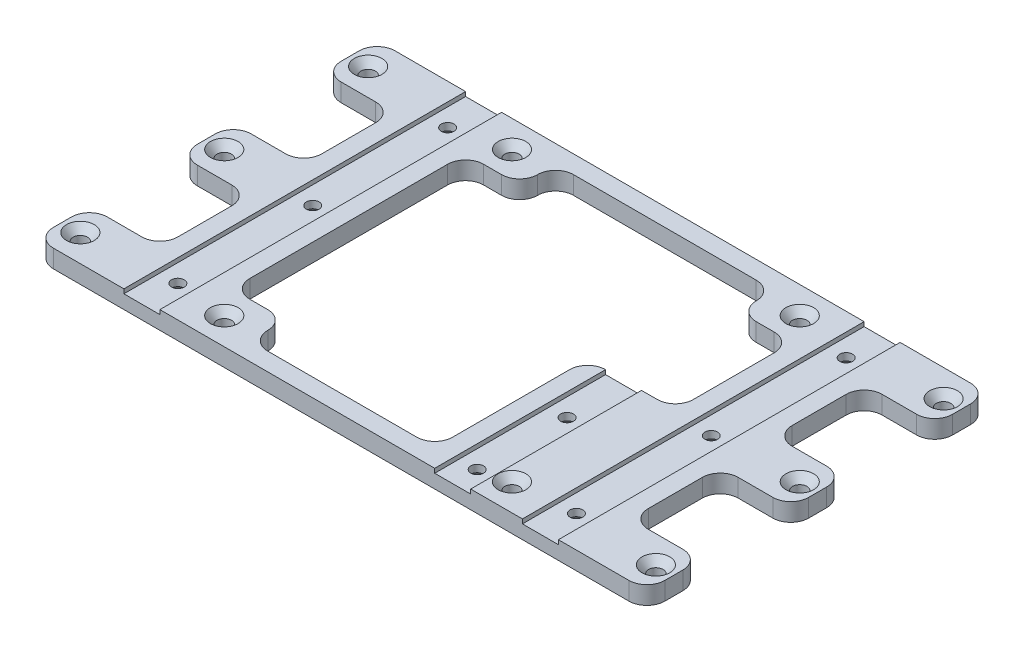
SolidWorks part; units mm, degrees
material "6061-T6 (SS)"
ref_plane "Front Plane" through (0, 0, 0) normal (0, 0, 1) x (1, 0, 0)
ref_plane "Top Plane" through (0, 0, 0) normal (0, 1, 0) x (1, 0, 0)
ref_plane "Right Plane" through (0, 0, 0) normal (1, 0, 0) x (0, 0, -1)
sketch "Sketch1" plane through (0, 0, 0) normal (0, 1, 0) x (1, 0, 0)
  line L1 (0, 0) -> (215.9, 0)
  line L2 (0, 0) -> (0, 120.65)
  line L3 (0, 120.65) -> (215.9, 120.65)
  line L4 (215.9, 0) -> (215.9, 120.65)
  dimension "D1" = 120.65
  dimension "D2" = 215.9
extrude "Boss-Extrude1" add sketch "Sketch1" along normal blind 6.35
hole_wizard "CSK for #10 Flat Head Machine Screw1" positions "Sketch3" profile "Sketch2" countersink size "#10" standard "Ansi Inch" end condition through all
sketch "Sketch3" plane through (0, 6.35, 0) normal (0, 1, 0) x (-1, 0, 0)
  line L0 (-107.95, 0) -> (-107.95, -120.65) construction
  line L1 (0, 0) -> (-215.9, 0) construction
  line L2 (-215.9, -120.65) -> (0, -120.65) construction
  line L4 (-215.9, -60.325) -> (0, -60.325) construction
  line L5 (-215.9, 0) -> (-215.9, -120.65) construction
  line L6 (0, -120.65) -> (0, 0) construction
  line L7 (-6.35, -111.125) -> (-209.55, -111.125) construction
  line L9 (-209.55, -111.125) -> (-209.55, -9.525) construction
  line L11 (-6.35, -111.125) -> (-6.35, -9.525) construction
  line L13 (-209.55, -9.525) -> (-6.35, -9.525) construction
  point P0 (-6.35, -111.125)
  point P1 (-209.55, -111.125)
  point P3 (-209.55, -9.525)
  point P5 (-6.35, -9.525)
  point P33 (-107.95, -111.125)
  point P41 (-6.35, -60.325)
  point P44 (-209.55, -60.325)
  point P54 (-158.75, -111.125)
  point P56 (-57.15, -111.125)
  point P58 (-57.15, -9.525)
  point P60 (-158.75, -9.525)
  dimension "D1" = 203.2
  dimension "D2" = 101.6
  dimension "D3" = 50.8
  dimension "D4" = 50.8
  dimension "D5" = 50.8
  dimension "D6" = 50.8
sketch "Sketch2" plane through (6.35, 6.35, -111.125) normal (1, 0, 0) x (0, 0, 1)
  line L0 (0, 0) -> (0, 6.35)
  line L1 (0, 6.35) -> (2.5527, 6.35)
  line L2 (2.5527, 6.35) -> (2.5527, 2.6882)
  line L3 (2.5527, 2.6882) -> (4.8895, 0)
  line L5 (4.8895, 0) -> (0, 0)
  line L6 (-2.5527, 2.6882) -> (-4.8895, 0) construction
  line L11 (0, -6.35) -> (0, 107.95) construction
  dimension "Thru Hole Dia." = 5.1054
  dimension "Thru Hole Depth" = 6.35
  dimension "Near C'Sink Dia." = 9.779
  dimension "Near C'Sink Angle" = 82
hole_wizard "CSK for #8 Flat Head Machine Screw1" positions "Sketch5" profile "Sketch6" countersink size "#8" standard "Ansi Inch" end condition through all
sketch "Sketch5" plane through (0, 0, 0) normal (0, -1, 0) x (1, 0, 0)
  line L0 (37.592, -12.7) -> (37.592, -107.95) construction
  line L3 (0, 0) -> (215.9, 0) construction
  line L5 (107.95, 0) -> (107.95, -120.65) construction
  line L6 (215.9, -120.65) -> (0, -120.65) construction
  point P0 (37.592, -12.7)
  point P8 (37.592, -60.325)
  point P10 (37.592, -107.95)
  point P27 (107.95, -60.325)
  dimension "D1" = 95.25
  dimension "D2" = 70.358
sketch "Sketch6" plane through (37.592, 0, -12.7) normal (1, 0, 0) x (0, 0, -1)
  line L0 (0, 0) -> (0, 6.35)
  line L1 (0, 6.35) -> (2.2479, 6.35)
  line L2 (2.2479, 6.35) -> (2.2479, 2.2645)
  line L3 (2.2479, 2.2645) -> (4.2164, 0)
  line L5 (4.2164, 0) -> (0, 0)
  line L6 (-2.2479, 2.2645) -> (-4.2164, 0) construction
  line L11 (0, -6.35) -> (0, 107.95) construction
  dimension "Thru Hole Dia." = 4.4958
  dimension "Thru Hole Depth" = 6.35
  dimension "Near C'Sink Dia." = 8.4328
  dimension "Near C'Sink Angle" = 82
ref_plane "Plane1" through (107.95, 0, 0) normal (-1, 0, 0) x (0, 0, 1)
mirror "Mirror1" about plane through (107.95, 0, 0) normal (-1, 0, 0) of "CSK for #8 Flat Head Machine Screw1"
hole_wizard "CSK for #8 Flat Head Machine Screw2" positions "Sketch8" profile "Sketch9" countersink size "#8" standard "Ansi Inch" end condition through all
sketch "Sketch8" plane through (0, 0, 0) normal (0, -1, 0) x (1, 0, 0)
  line L0 (147.3359, -8.636) -> (147.3359, -40.386) construction
  line L4 (0, 0) -> (215.9, 0) construction
  circle A2 centre (178.308, -12.7) radius 4.2164 construction
  point P0 (147.3359, -8.636)
  point P8 (147.3359, -40.386)
  dimension "D3" = 30.9721
  dimension "D1" = 31.75
  dimension "D2" = 8.636
sketch "Sketch9" plane through (147.3359, 0, -8.636) normal (1, 0, 0) x (0, 0, -1)
  line L0 (0, 0) -> (0, 6.35)
  line L1 (0, 6.35) -> (2.2479, 6.35)
  line L2 (2.2479, 6.35) -> (2.2479, 2.2645)
  line L3 (2.2479, 2.2645) -> (4.2164, 0)
  line L5 (4.2164, 0) -> (0, 0)
  line L6 (-2.2479, 2.2645) -> (-4.2164, 0) construction
  line L11 (0, -6.35) -> (0, 107.95) construction
  dimension "Thru Hole Dia." = 4.4958
  dimension "Thru Hole Depth" = 6.35
  dimension "Near C'Sink Dia." = 8.4328
  dimension "Near C'Sink Angle" = 82
sketch "Sketch10" plane through (0, 6.35, 0) normal (0, 1, 0) x (1, 0, 0)
  line L0 (37.592, 120.65) -> (37.592, 0) construction
  line L1 (215.9, 120.65) -> (0, 120.65) construction
  line L2 (0, 0) -> (215.9, 0) construction
  line L3 (178.308, 120.65) -> (178.308, 0) construction
  line L4 (147.3359, 120.65) -> (147.3359, 0) construction
  line L5 (37.592, 19.05) -> (37.592, 0) construction
  line L6 (178.308, 6.35) -> (178.308, 0) construction
  line L7 (147.3359, 8.636) -> (147.3359, 0) construction
  line L8 (31.242, 120.65) -> (31.242, 0)
  line L9 (171.958, 120.65) -> (171.958, 0)
  line L10 (140.9859, 63.5) -> (140.9859, 0)
  line L11 (43.942, 120.65) -> (43.942, 0)
  line L12 (184.658, 120.65) -> (184.658, 0)
  line L13 (153.6859, 63.5) -> (153.6859, 0)
  line L14 (31.242, 120.65) -> (43.942, 120.65)
  line L15 (43.942, 0) -> (31.242, 0)
  line L16 (171.958, 0) -> (184.658, 0)
  line L17 (140.9859, 0) -> (153.6859, 0)
  line L18 (171.958, 120.65) -> (184.658, 120.65)
  line L19 (140.9859, 120.65) -> (140.9859, 0) construction
  line L20 (37.592, 107.95) -> (37.592, 120.65) construction
  line L21 (215.9, 120.65) -> (0, 120.65) construction
  line L22 (178.308, 107.95) -> (178.308, 120.65) construction
  line L23 (147.3359, 107.95) -> (147.3359, 120.65) construction
  line L24 (153.6859, 120.65) -> (153.6859, 0) construction
  line L25 (140.9859, 63.5) -> (153.6859, 63.5)
  line L26 (215.9, 120.65) -> (0, 120.65) construction
  dimension "D3" = 57.15
  dimension "D1" = 6.35
  dimension "D2" = 6.35
extrude "Cut-Extrude1" cut sketch "Sketch10" against normal blind 1.524
sketch "Sketch13" plane through (0, 6.35, 0) normal (0, 1, 0) x (1, 0, 0)
  line L0 (0, 120.65) -> (0, 0) construction
  line L1 (0, 101.6) -> (24.892, 101.6)
  line L2 (0, 101.6) -> (0, 69.85)
  line L3 (0, 69.85) -> (24.892, 69.85)
  line L4 (24.892, 101.6) -> (24.892, 69.85)
  line L5 (24.892, 69.85) -> (24.892, 50.8) construction
  line L6 (0, 50.8) -> (24.892, 50.8)
  line L7 (0, 50.8) -> (0, 19.05)
  line L8 (0, 19.05) -> (24.892, 19.05)
  line L9 (24.892, 50.8) -> (24.892, 19.05)
  line L10 (0, 120.65) -> (215.9, 120.65) construction
  line L11 (107.95, 120.65) -> (107.95, 0) construction
  line L12 (43.942, 0) -> (140.9859, 0) construction
  line L13 (24.892, 60.325) -> (107.95, 60.325) construction
  line L14 (31.242, 120.65) -> (31.242, 0) construction
  circle A0 centre (6.35, 111.125) radius 2.5527 construction
  dimension "D2" = 9.525
  dimension "D1" = 19.05
  dimension "D3" = 6.35
extrude "Cut-Extrude2" cut sketch "Sketch13" against normal through all
mirror "Mirror4" about plane through (107.95, 0, 0) normal (-1, 0, 0) of "Cut-Extrude2"
fillet "Fillet2" radius 6.35 20 edges at (0, 3.175, 0) (0, 3.175, -19.05) (24.892, 3.175, -19.05) (0, 3.175, -120.65) (0, 3.175, -101.6) (24.892, 3.175, -50.8) (0, 3.175, -50.8) (0, 3.175, -69.85) (24.892, 3.175, -69.85) (24.892, 3.175, -101.6) (215.9, 3.175, -120.65) (215.9, 3.175, -101.6) (191.008, 3.175, -101.6) (191.008, 3.175, -69.85) (191.008, 3.175, -19.05) (191.008, 3.175, -50.8) (215.9, 3.175, -69.85) (215.9, 3.175, -50.8) (215.9, 3.175, -19.05) (215.9, 3.175, 0)
sketch "Sketch14" plane through (0, 6.35, 0) normal (0, 1, 0) x (1, 0, 0)
  line L0 (18.542, 101.6) -> (6.35, 101.6) construction
  line L1 (43.942, 120.65) -> (69.342, 120.65)
  line L2 (43.942, 120.65) -> (43.942, 101.6)
  line L3 (43.942, 101.6) -> (69.342, 101.6)
  line L4 (69.342, 120.65) -> (69.342, 101.6)
  line L5 (43.942, 0) -> (69.342, 0)
  line L6 (43.942, 0) -> (43.942, 19.05)
  line L7 (43.942, 19.05) -> (69.342, 19.05)
  line L8 (69.342, 0) -> (69.342, 19.05)
  line L9 (171.958, 0) -> (134.6359, 0)
  line L10 (171.958, 0) -> (171.958, 19.05)
  line L11 (171.958, 19.05) -> (134.6359, 19.05)
  line L12 (134.6359, 60.325) -> (134.6359, 0)
  line L13 (171.958, 120.65) -> (146.558, 120.65)
  line L14 (171.958, 120.65) -> (171.958, 101.6)
  line L15 (171.958, 101.6) -> (146.558, 101.6)
  line L16 (146.558, 120.65) -> (146.558, 101.6)
  line L17 (6.35, 19.05) -> (18.542, 19.05) construction
  line L19 (50.292, 101.6) -> (50.292, 19.05)
  line L20 (140.9859, 63.5) -> (140.9859, 0) construction
  line L21 (134.6359, 60.325) -> (165.608, 60.325)
  line L22 (165.608, 60.325) -> (165.608, 101.6)
  line L23 (43.942, 0) -> (43.942, 120.65) construction
  line L24 (171.958, 120.65) -> (171.958, 0) construction
  line L25 (69.342, 114.3) -> (146.558, 114.3)
  line L26 (69.342, 6.35) -> (134.6359, 6.35)
  line L27 (171.958, 120.65) -> (43.942, 120.65) construction
  line L28 (43.942, 0) -> (140.9859, 0) construction
  line M4 (140.9859, 0) -> (140.9859, 63.5)
  line M38 (140.9859, 63.5) -> (153.6859, 63.5)
  line M39 (153.6859, 63.5) -> (153.6859, 0)
  dimension "D1" = 25.4
  dimension "D2" = 6.35
  dimension "D3" = 25.4
  dimension "D4" = 6.35
  dimension "D5" = 6.35
  dimension "D6" = 60.325
  dimension "D7" = 6.35
  dimension "D8" = 6.35
extrude "Cut-Extrude4" cut sketch "Sketch14" against normal through all contours L8 L26 L12 L21 L22 L15 L16 L25 L4 L3 L19 L7 M4 M38 M39 | L21 M4 M39 M38 region at (101.9121, 6.35, -63.6744) region at (147.3359, 6.35, -61.9125)
fillet "Fillet4" radius 6.35 12 edges at (165.608, 3.175, -101.6) (134.6359, 3.175, -6.35) (69.342, 3.175, -6.35) (50.292, 3.175, -19.05) (50.292, 3.175, -101.6) (69.342, 3.175, -114.3) (146.558, 3.175, -114.3) (69.342, 3.175, -19.05) (69.342, 3.175, -101.6) (146.558, 3.175, -101.6) (165.608, 3.175, -60.325) (134.6359, 3.175, -60.325)
